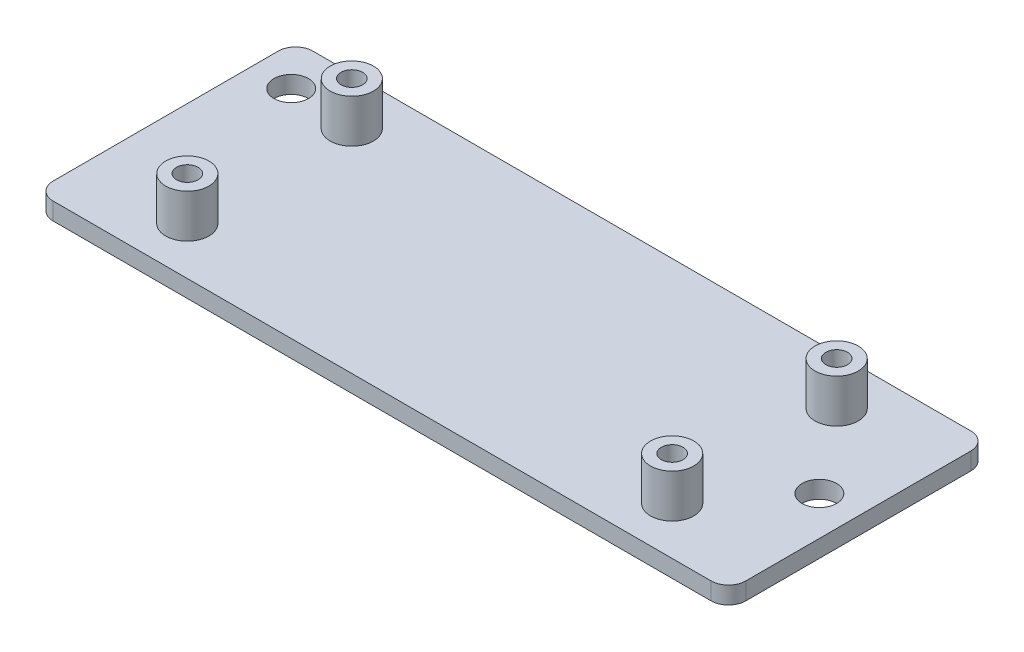
SolidWorks part; units mm, degrees
material "ABS"
ref_plane "Спереди" through (0, 0, 0) normal (0, 0, 1) x (1, 0, 0)
ref_plane "Сверху" through (0, 0, 0) normal (0, 1, 0) x (1, 0, 0)
ref_plane "Справа" through (0, 0, 0) normal (1, 0, 0) x (0, 0, -1)
sketch "Эскиз1" plane through (0, 0, 0) normal (0, 1, 0) x (1, 0, 0)
  line L1 (0, 0) -> (80, 0)
  line L2 (0, 0) -> (0, -30)
  line L3 (0, -30) -> (80, -30)
  line L4 (80, 0) -> (80, -30)
  dimension "D1" = 30
  dimension "D2" = 80
extrude "Бобышка-Вытянуть1" add sketch "Эскиз1" along normal blind 2
sketch "Эскиз2" plane through (0, 2, 0) normal (0, 1, 0) x (1, 0, 0)
  line L0 (0, 0) -> (0, -30) construction
  line L1 (80, 0) -> (0, 0) construction
  line L3 (0, -30) -> (80, -30) construction
  line L4 (80, -30) -> (80, 0) construction
  circle A0 centre (12, -5.5) radius 2.5
  circle A1 centre (12, -24.5) radius 2.5
  circle A2 centre (68, -5.5) radius 2.5
  circle A3 centre (68, -24.5) radius 2.5
  dimension "D1" = 12
  dimension "D2" = 5.5
  dimension "D3" = 12
  dimension "D4" = 5.5
  dimension "D5" = 12
  dimension "D6" = 5.5
  dimension "D7" = 12
  dimension "D8" = 5.5
  dimension "D9" = 5
  dimension "D10" = 5
  dimension "D11" = 5
  dimension "D12" = 5
extrude "Бобышка-Вытянуть2" add sketch "Эскиз2" along normal blind 5
sketch "Эскиз3" plane through (0, 7, 0) normal (0, 1, 0) x (1, 0, 0)
  circle A0 centre (12, -5.5) radius 1.25
  circle A1 centre (12, -24.5) radius 1.25
  circle A2 centre (68, -5.5) radius 1.25
  circle A3 centre (68, -24.5) radius 1.25
  dimension "D1" = 2.5
  dimension "D2" = 2.5
  dimension "D3" = 2.5
  dimension "D4" = 2.5
extrude "Вырез-Вытянуть1" cut sketch "Эскиз3" against normal through all both and the other way through all
sketch "Эскиз4" plane through (0, 2, 0) normal (0, 1, 0) x (1, 0, 0)
  line L0 (0, -15) -> (80, -15) construction
  line L1 (0, 0) -> (0, -30) construction
  line L2 (80, -30) -> (80, 0) construction
  line L3 (80, 0) -> (0, 0) construction
  circle A0 centre (4.5, -5) radius 2
  circle A1 centre (75.5, -15) radius 2
  dimension "D1" = 4.5
  dimension "D2" = 4
  dimension "D3" = 4.5
  dimension "D4" = 4
  dimension "D5" = 5
extrude "Вырез-Вытянуть2" cut sketch "Эскиз4" against normal through all both and the other way through all
fillet "Скругление1" radius 2 1 edges at (0, 1, 30) type face fillet first side face at (0, 1, 15) second side face at (40, 1, 30)
fillet "Скругление2" radius 2 1 edges at (0, 1, 0) type face fillet first side face at (40, 1, 0) second side face at (0, 1, 14)
fillet "Скругление3" radius 2 1 edges at (80, 1, 0) type face fillet first side face at (41, 1, 0) second side face at (80, 1, 15)
fillet "Скругление4" radius 2 1 edges at (80, 1, 30) type face fillet first side face at (80, 1, 16) second side face at (41, 1, 30)
